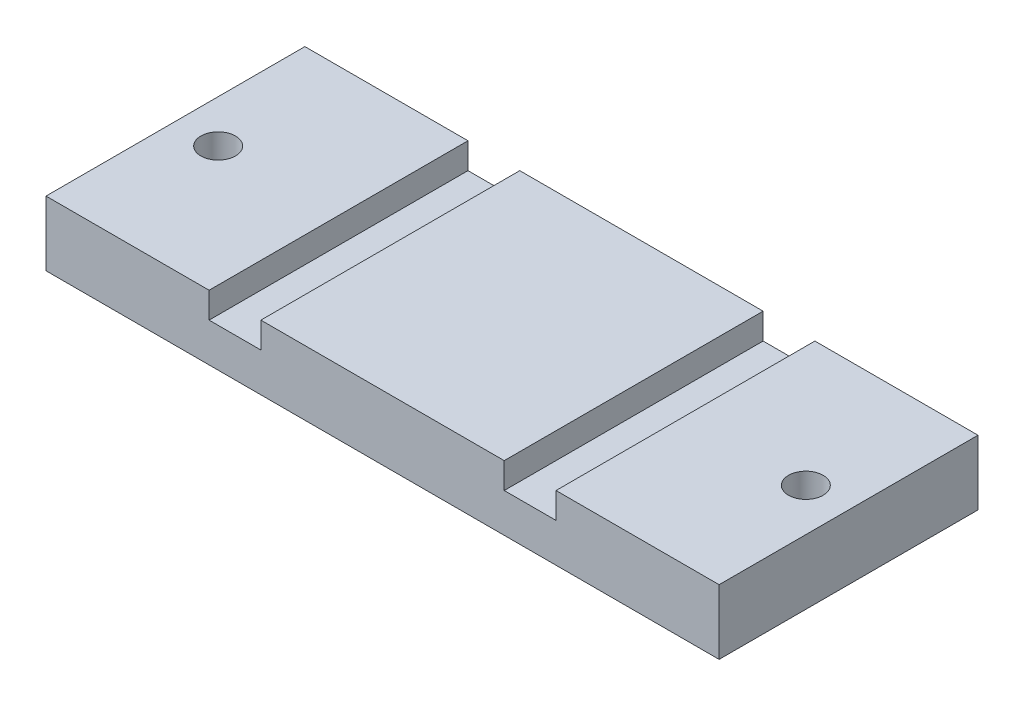
SolidWorks part; units mm, degrees
material "Delrin 2700 NC010, Low Viscosity Acetal Copolymer (SS)"
ref_plane "Front Plane" through (0, 0, 0) normal (0, 0, 1) x (1, 0, 0)
ref_plane "Top Plane" through (0, 0, 0) normal (0, 1, 0) x (1, 0, 0)
ref_plane "Right Plane" through (0, 0, 0) normal (1, 0, 0) x (0, 0, -1)
sketch "Sketch1" plane through (0, 0, 0) normal (0, 1, 0) x (1, 0, 0)
  line L1 (0, 0) -> (66.04, 0)
  line L2 (0, 0) -> (0, 25.4)
  line L3 (0, 25.4) -> (66.04, 25.4)
  line L4 (66.04, 0) -> (66.04, 25.4)
  dimension "D1" = 66.04
  dimension "D2" = 25.4
extrude "Boss-Extrude1" add sketch "Sketch1" along normal blind 6.35
hole_wizard "M3 Clearance Hole1" positions "Sketch4" profile "Sketch3" hole size "M3" standard "ANSI Metric" end condition through all
sketch "Sketch4" plane through (0, 6.35, 0) normal (0, 1, 0) x (1, 0, 0)
  line L0 (0, 12.7) -> (66.04, 12.7) construction
  line L1 (0, 25.4) -> (0, 0) construction
  line L2 (66.04, 0) -> (66.04, 25.4) construction
  line L4 (33.02, 0) -> (33.02, 25.4) construction
  line L5 (0, 0) -> (66.04, 0) construction
  line L6 (66.04, 25.4) -> (0, 25.4) construction
  point P0 (4.191, 12.7)
  point P2 (61.849, 12.7)
  dimension "D1" = 28.829
  dimension "D2" = 28.829
sketch "Sketch3" plane through (4.191, 6.35, -12.7) normal (1, 0, 0) x (0, 0, 1)
  line L0 (0, 0) -> (0, 6.35)
  line L1 (0, 6.35) -> (1.7, 6.35)
  line L2 (1.7, 6.35) -> (1.7, 0)
  line L5 (1.7, 0) -> (0, 0)
  line L11 (0, -6.35) -> (0, 107.95) construction
  dimension "Thru Hole Dia." = 3.4
  dimension "Thru Hole Depth" = 6.35
sketch "Sketch5" plane through (0, 0, 0) normal (0, 0, 1) x (1, 0, 0)
  line L0 (33.02, 6.35) -> (33.02, 0) construction
  line L5 (0, 6.35) -> (66.04, 6.35) construction
  line L6 (0, 0) -> (66.04, 0) construction
  line L7 (50.038, 3.81) -> (44.958, 3.81)
  line L8 (16.002, 6.35) -> (21.082, 6.35)
  line L9 (16.002, 6.35) -> (16.002, 3.81)
  line L10 (16.002, 3.81) -> (21.082, 3.81)
  line L11 (21.082, 6.35) -> (21.082, 3.81)
  line L12 (44.958, 6.35) -> (44.958, 3.81)
  line L13 (50.038, 6.35) -> (44.958, 6.35)
  line L14 (50.038, 6.35) -> (50.038, 3.81)
  dimension "D1" = 5.08
  dimension "D2" = 11.938
  dimension "D3" = 2.54
extrude "Cut-Extrude1" cut sketch "Sketch5" against normal through all
equation "\"spool lenght\"= 45mm"
equation "\"hole distance\"= 0.25in"
equation "\"D2@Sketch4\"=\"spool lenght\"/2 + \"hole distance\""
equation "\"D1@Sketch4\"=\"spool lenght\"/2 + \"hole distance\""
equation "\"tooth clearance\" =0.09"
equation "\"tooth thickness\"= .09"
equation "\"center distance\" = ( 1.42 / 2 ) - 0.2"
equation "\"D2@Sketch5\"=\"center distance\" - 4*\"clearance\""
equation "\"clearance\"= .005"
equation "\"D3@Sketch5\"=\"tooth clearance\" + \"clearance\""
